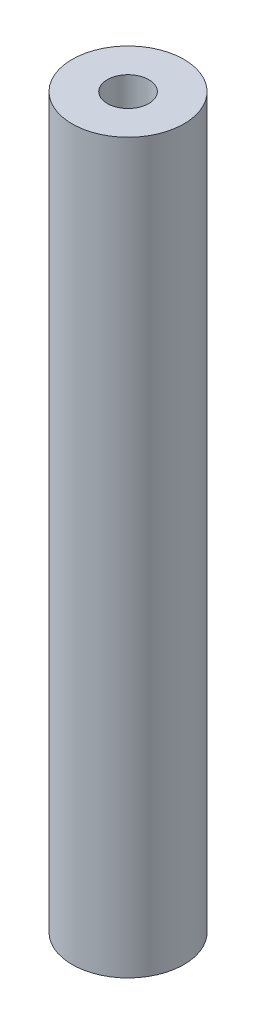
SolidWorks part; units mm, degrees
material "ABS"
ref_plane "Front Plane" through (0, 0, 0) normal (0, 0, 1) x (1, 0, 0)
ref_plane "Top Plane" through (0, 0, 0) normal (0, 1, 0) x (1, 0, 0)
ref_plane "Right Plane" through (0, 0, 0) normal (1, 0, 0) x (0, 0, -1)
sketch "Sketch1" plane through (0, 0, 0) normal (0, 1, 0) x (1, 0, 0)
  circle A0 centre (0, 0) radius 2.1209
  circle A1 centre (0, 0) radius 5.715
  dimension "D1" = 4.2418
  dimension "D2" = 11.43
extrude "Boss-Extrude1" add sketch "Sketch1" along normal blind 74.422
